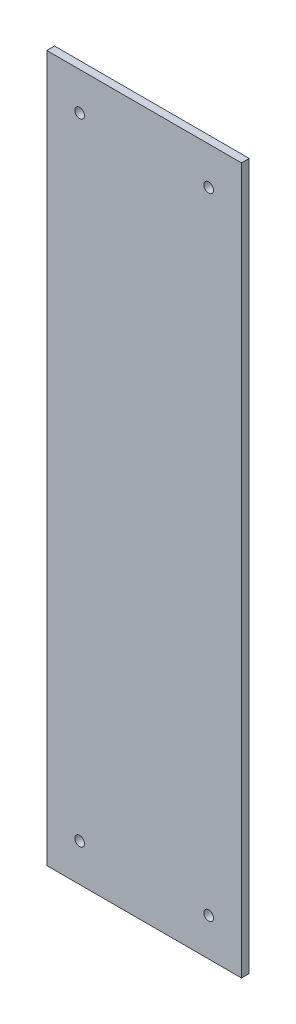
SolidWorks part; units mm, degrees
ref_plane "Front Plane" through (0, 0, 0) normal (0, 0, 1) x (1, 0, 0)
ref_plane "Top Plane" through (0, 0, 0) normal (0, 1, 0) x (1, 0, 0)
ref_plane "Right Plane" through (0, 0, 0) normal (1, 0, 0) x (0, 0, -1)
sketch "Sketch1" plane through (0, 0, 0) normal (0, 0, 1) x (1, 0, 0)
  line L0 (0, 145) -> (0, -145) construction
  line L1 (-40, -145) -> (40, -145)
  line L2 (-40, -145) -> (-40, 145)
  line L3 (-40, 145) -> (40, 145)
  line L4 (40, -145) -> (40, 145)
  line L5 (-40, -145) -> (40, 145) construction
  line L6 (-40, 145) -> (40, -145) construction
  line L7 (-40, 0) -> (40, 0) construction
  circle A0 centre (26.5, 129.5) radius 2
  circle A1 centre (-26.5, 129.5) radius 2
  circle A2 centre (26.5, -129.5) radius 2
  circle A3 centre (-26.5, -129.5) radius 2
  point P0 (0, 0)
  dimension "D3" = 4
  dimension "D1" = 26.5
  dimension "D2" = 129.5
  dimension "D4" = 145
  dimension "D5" = 40
extrude "Boss-Extrude1" add sketch "Sketch1" along normal mid plane 3.175 contours A3 | L3 L4 L1 L2 | A1 | A0 | A2 region at (-26.5, -129.5, 0)
